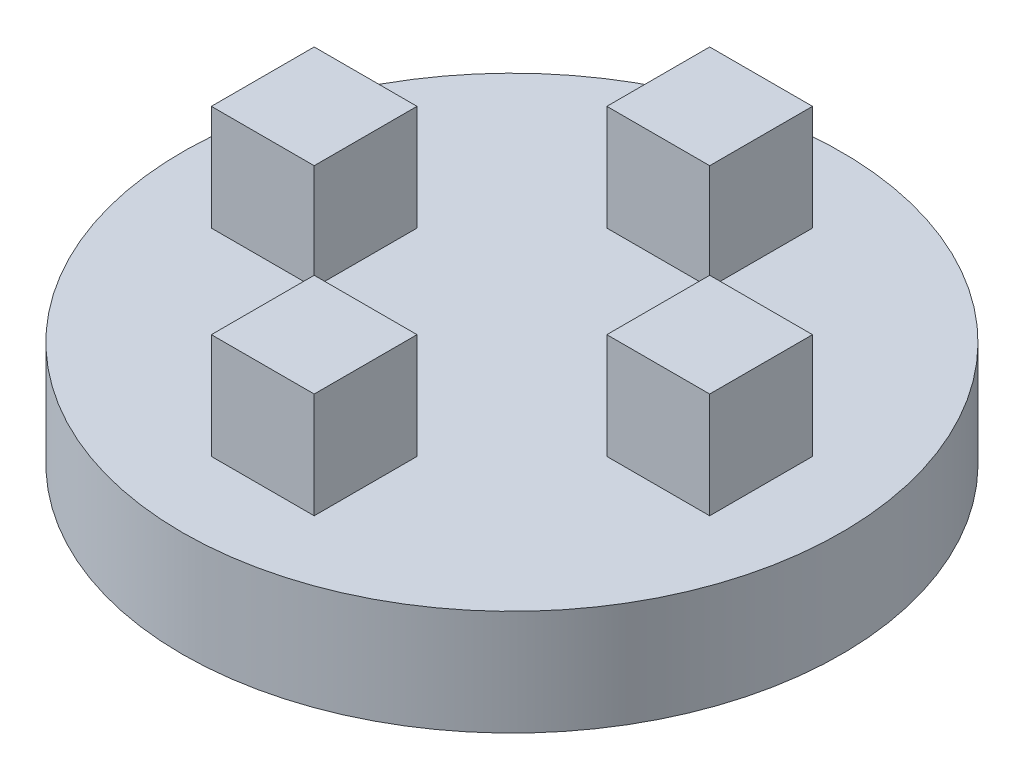
SolidWorks part; units mm, degrees
ref_plane "Front Plane" through (0, 0, 0) normal (0, 0, 1) x (1, 0, 0)
ref_plane "Top Plane" through (0, 0, 0) normal (0, 1, 0) x (1, 0, 0)
ref_plane "Right Plane" through (0, 0, 0) normal (1, 0, 0) x (0, 0, -1)
sketch "Sketch1" plane through (0, 0, 0) normal (0, 1, 0) x (1, 0, 0)
  circle A0 centre (0, 0) radius 12.5
  dimension "D1" = 25
extrude "Boss-Extrude1" add sketch "Sketch1" along normal mid plane 4
sketch "Sketch2" plane through (0, 2, 0) normal (0, 1, 0) x (1, 0, 0)
  line L1 (-2, 9.5) -> (2, 9.5) construction
  line L2 (-2, 9.5) -> (-2, 5.5) construction
  line L3 (-2, 5.5) -> (2, 5.5) construction
  line L4 (2, 9.5) -> (2, 5.5) construction
  line L5 (-1.95, 9.45) -> (-1.95, 5.55)
  line L6 (-1.95, 5.55) -> (1.95, 5.55)
  line L7 (1.95, 9.45) -> (1.95, 5.55)
  line L8 (-1.95, 9.45) -> (1.95, 9.45)
  line L9 (9.45, 1.95) -> (5.55, 1.95)
  line L10 (5.55, 1.95) -> (5.55, -1.95)
  line L11 (9.45, -1.95) -> (5.55, -1.95)
  line L12 (9.45, 1.95) -> (9.45, -1.95)
  line L13 (1.95, -9.45) -> (1.95, -5.55)
  line L14 (1.95, -5.55) -> (-1.95, -5.55)
  line L15 (-1.95, -9.45) -> (-1.95, -5.55)
  line L16 (1.95, -9.45) -> (-1.95, -9.45)
  line L17 (-9.45, -1.95) -> (-5.55, -1.95)
  line L18 (-5.55, -1.95) -> (-5.55, 1.95)
  line L19 (-9.45, 1.95) -> (-5.55, 1.95)
  line L20 (-9.45, -1.95) -> (-9.45, 1.95)
  point P4 (0, 5.5)
  point P25 (0, 0)
  dimension "D1" = 5.5
  dimension "D2" = 4
  dimension "D3" = 4
  dimension "D4" = 0.05
  dimension "D5" = 4
extrude "Boss-Extrude3" add sketch "Sketch2" along normal blind 4
sketch "Sketch3" plane through (0, -2, 0) normal (0, -1, 0) x (1, 0, 0)
  circle A0 centre (0, 0) radius 5
  dimension "D1" = 10
extrude "Boss-Extrude4" add sketch "Sketch3" along normal blind 1
sketch "Sketch4" plane through (0, -3, 0) normal (0, -1, 0) x (1, 0, 0)
  line L1 (0, -3.7) -> (3.2043, -1.85)
  line L2 (3.2043, -1.85) -> (3.2043, 1.85)
  line L3 (3.2043, 1.85) -> (0, 3.7)
  line L4 (0, 3.7) -> (-3.2043, 1.85)
  line L5 (-3.2043, 1.85) -> (-3.2043, -1.85)
  line L6 (-3.2043, -1.85) -> (0, -3.7)
  circle A0 centre (0, 0) radius 3.7 construction
  circle A1 centre (0, 0) radius 3.2043 construction
  dimension "D1" = 7.4
extrude "Boss-Extrude5" add sketch "Sketch4" along normal blind 5
